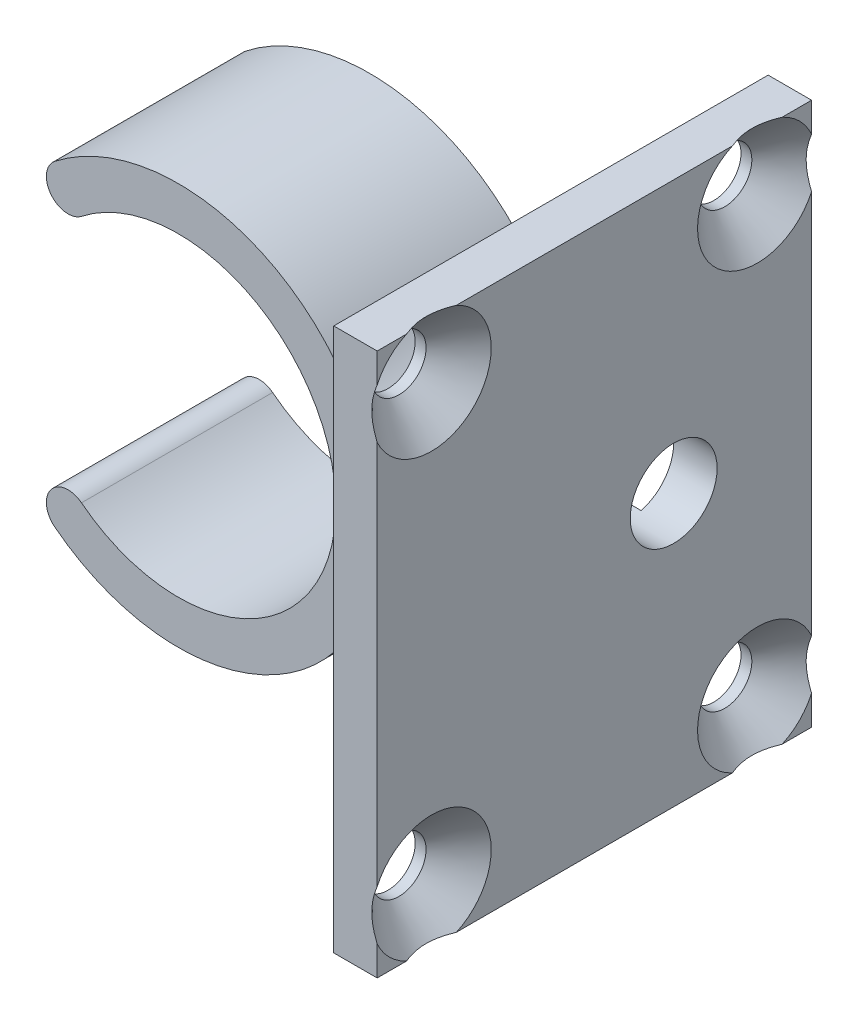
SolidWorks part; units mm, degrees
ref_plane "Спереди" through (0, 0, 0) normal (0, 0, 1) x (1, 0, 0)
ref_plane "Сверху" through (0, 0, 0) normal (0, 1, 0) x (1, 0, 0)
ref_plane "Справа" through (0, 0, 0) normal (1, 0, 0) x (0, 0, -1)
sketch "Эскиз1" plane through (0, 0, 0) normal (0, 0, 1) x (1, 0, 0)
  line L0 (9.25, 0) -> (0, 0) construction
  arc A0 (-4.4648, -5.7121) -> (-4.4648, 5.7121) centre (0, 0) ccw
  arc A1 (-5.6964, -7.2879) -> (-5.6964, 7.2879) centre (0, 0) ccw
  arc A2 (-5.6964, 7.2879) -> (-4.4648, 5.7121) centre (-5.0806, 6.5) ccw
  arc A3 (-5.6964, -7.2879) -> (-4.4648, -5.7121) centre (-5.0806, -6.5) cw
  dimension "D2" = 7.25
  dimension "D3" = 2
  dimension "D1" = 13
extrude "Выталкивающая часть (С ПАЗАМИ В ОБЕ СТОРОНЫ ВЫДАВИТЬ НА 5ММ)" add sketch "Эскиз1" along normal blind 4.8 and the other way blind 4
sketch "Эскиз2" plane through (0, 0, 0) normal (0, 0, 1) x (1, 0, 0)
  line L0 (0, 0) -> (22.4907, 0) construction
  line L11 (12.5, 3.75) -> (12.5, -3.75)
  arc A0 (7.2461, -5.7495) -> (7.2461, 5.7495) centre (0, 0) ccw
  arc A1 (-5.6964, -7.2879) -> (-5.6964, 7.2879) centre (0, 0) ccw construction
  arc A3 (7.2461, 5.7495) -> (12.5, 3.75) centre (11.5546, 9.1681) ccw
  arc A4 (7.2461, -5.7495) -> (12.5, -3.75) centre (11.5546, -9.1681) cw
  point P6 (12.5, 0)
  dimension "D1" = 7.5
  dimension "D3" = 12.5
  dimension "D2" = 5.5
extrude "Наплыв для крепления" add sketch "Эскиз2" along normal up to surface (4.8 mm away) and the other way up to surface (4 mm away) up to face at (1.1908, 0, 4.8) other way up to face at (1.1908, 0, -4)
sketch "Эскиз3" plane through (0, 0, 0) normal (0, 0, 1) x (1, 0, 0)
  line L0 (12.5, -12.5) -> (12.5, 12.5)
  line L1 (12.5, 12.5) -> (15.5, 12.5)
  line L2 (15.5, 12.5) -> (15.5, -12.5)
  line L3 (15.5, -12.5) -> (12.5, -12.5)
  line L5 (12.5, -3.75) -> (12.5, 3.75) construction
  point P9 (12.5, 0)
  point P10 (12.5, 0)
  dimension "D1" = 3
  dimension "D2" = 25
extrude "Пластина для фиксации" [suppressed] add sketch "Эскиз3" along normal blind 8.35 and the other way blind 8.35
sketch "Эскиз5" [suppressed] plane through (0, 12.5, 0) normal (0, 1, 0) x (1, 0, 0)
  line L0 (10.5, 8.35) -> (10.5, 7.35)
  line L1 (12.5, 8.35) -> (9.5, 8.35) construction
  line L2 (10.5, 7.35) -> (11.5, 7.35)
  line L3 (11.5, 7.35) -> (11.5, 8.35)
  line L4 (11.5, 8.35) -> (10.5, 8.35)
  line L5 (12.5, 0) -> (9.5, 0) construction
  line L6 (12.5, 8.35) -> (12.5, -8.35) construction
  line L7 (9.5, 5) -> (9.5, -5) construction
  line L8 (11.5, -8.35) -> (10.5, -8.35)
  line L9 (11.5, -7.35) -> (11.5, -8.35)
  line L10 (10.5, -7.35) -> (11.5, -7.35)
  line L11 (10.5, -8.35) -> (10.5, -7.35)
  point P7 (11, 8.35)
  point P8 (11, 8.35)
  dimension "D1" = 1
extrude "Пазы горизонтальные" [suppressed] cut sketch "Эскиз5" against normal through all
sketch "Эскиз6" [suppressed] plane through (12.5, 0, 0) normal (1, 0, 0) x (0, 0, -1)
  circle A0 centre (4.5, 0) radius 2
  dimension "D1" = 4
  dimension "D2" = 4.5
extrude "Под толкатель" [suppressed] cut sketch "Эскиз6" against normal through all
sketch "Эскиз7" [suppressed] plane through (0, 0, 8.35) normal (0, 0, 1) x (1, 0, 0)
  line L2 (11.3, 10.5) -> (11.3, 12.5)
  line L3 (12.5, 12.5) -> (9.5, 12.5) construction
  line L4 (11.3, 12.5) -> (12.5, 12.5)
  line L5 (12.5, 12.5) -> (12.5, 10.5)
  line L7 (12.5, 10.5) -> (11.3, 10.5)
  line L9 (12.5, -12.5) -> (12.5, 12.5) construction
  line L10 (0, 0) -> (12.5, 0) construction
  line L11 (12.5, -10.5) -> (11.3, -10.5)
  line L12 (12.5, -12.5) -> (12.5, -10.5)
  line L13 (11.3, -12.5) -> (12.5, -12.5)
  line L14 (11.3, -10.5) -> (11.3, -12.5)
  line L15 (9.5, 12.5) -> (9.5, -12.5) construction
  dimension "D1" = 2
  dimension "D2" = 1.8
extrude "Вертикальные пазы" [suppressed] cut sketch "Эскиз7" against normal through all
sketch "Эскиз8" plane through (12.5, 0, 0) normal (1, 0, 0) x (0, 0, -1)
  line L0 (-0.15, 12.5) -> (-0.15, -12.4045) construction
  line L1 (-10.15, 12.5) -> (9.85, 12.5)
  line L2 (-10.15, 12.5) -> (-10.15, -12.5)
  line L3 (-10.15, -12.5) -> (9.85, -12.5)
  line L4 (9.85, 12.5) -> (9.85, -12.5)
  line L5 (-10.15, 12.5) -> (9.85, -12.5) construction
  line L6 (-10.15, -12.5) -> (9.85, 12.5) construction
  line L7 (-10.15, 0) -> (9.85, 0) construction
  line L8 (-10.15, -12.5) -> (9.85, -12.5)
  line L9 (-4.8, -3.75) -> (-4.8, 3.75) construction
  circle A0 centre (-7.65, 10) radius 1.25
  circle A5 centre (-7.65, -10) radius 1.25
  circle A6 centre (7.35, -10) radius 1.25
  circle A7 centre (7.35, 10) radius 1.25
  point P0 (-0.15, 0)
  line M7 (-4.8, 3.75) -> (-4.8, -3.75)
  line M9 (4, -3.75) -> (4, 3.75)
  dimension "D4" = 2.5
  dimension "D1" = 25
  dimension "D2" = 20
  dimension "D3" = 4.65
  dimension "D5" = 2.5
  dimension "D6" = 2.5
extrude "Пластина для крепления на саморезы" add sketch "Эскиз8" along normal blind 2 contours L4 L1 L2 L3 A5 A0 A6 A7 M9 M7 | M9 M7 region at (12.5, 0, 0.15)
chamfer "Фаска2" distance 1.5 angle 45 4 edges at (14.5, 10, 6.4) (14.5, -10, 6.4) (14.5, -10, -8.6) (14.5, 10, -8.6)
sketch "Эскиз9" plane through (14.5, 0, 0) normal (1, 0, 0) x (0, 0, -1)
  circle A0 centre (3.5, 0) radius 2
  dimension "D1" = 4
  dimension "D2" = 3.5
extrude "Вырез под толкатель" cut sketch "Эскиз9" against normal up to next
